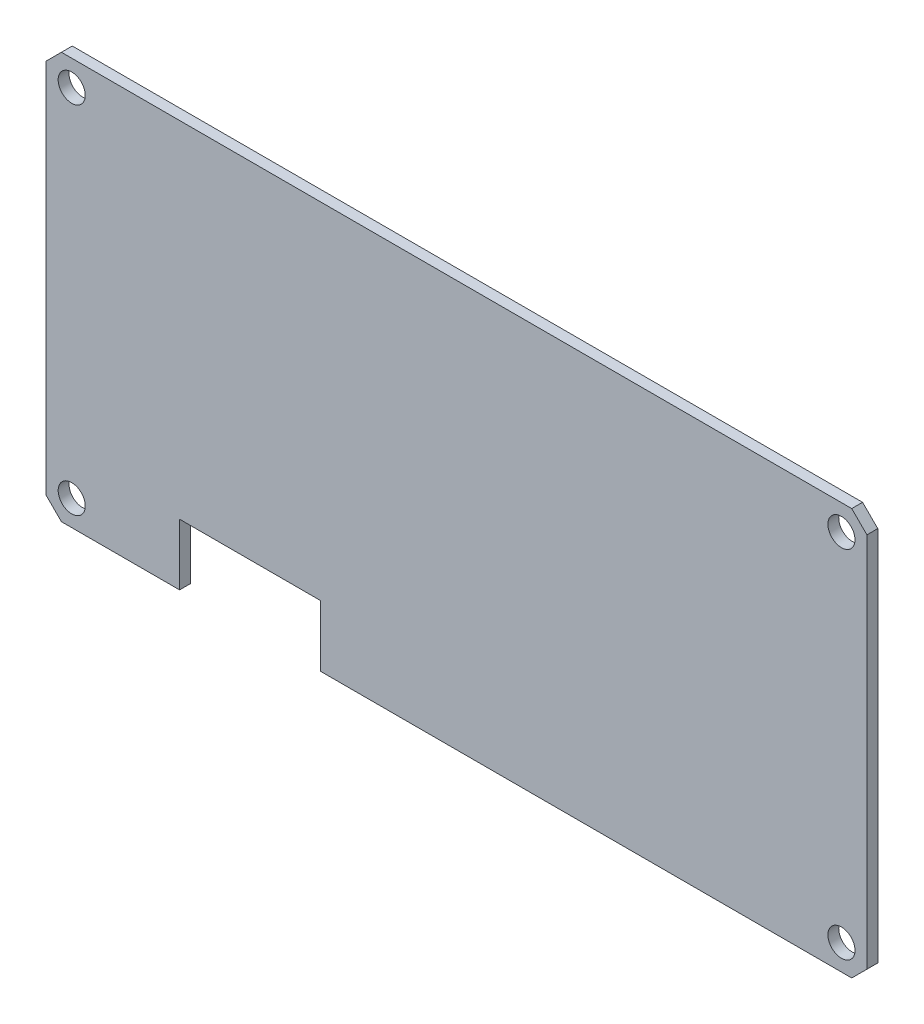
SolidWorks part; units mm, degrees
ref_plane "Front Plane" through (0, 0, 0) normal (0, 0, 1) x (1, 0, 0)
ref_plane "Top Plane" through (0, 0, 0) normal (0, 1, 0) x (1, 0, 0)
ref_plane "Right Plane" through (0, 0, 0) normal (1, 0, 0) x (0, 0, -1)
sketch "Sketch1" plane through (0, 0, 0) normal (0, 0, 1) x (1, 0, 0)
  line L1 (0, -18.75) -> (-33.8, -18.75)
  line L2 (0, -18.75) -> (0, 18.75)
  line L3 (0, 18.75) -> (-33.8, 18.75)
  line L4 (-33.8, -18.75) -> (-33.8, 18.75)
  line L5 (-31.8, -4.9) -> (-31.8, -14.1) construction
  dimension "D1" = 37.5
  dimension "D2" = 2
extrude "Boss-Extrude-NoAnt" add sketch "Sketch1" along normal blind 1
sketch "Sketch2" plane through (0, 0, 0) normal (0, 0, 1) x (1, 0, 0)
  line L1 (0, 18.75) -> (41.9, 18.75)
  line L2 (0, 18.75) -> (0, -18.75)
  line L3 (0, -18.75) -> (41.9, -18.75)
  line L4 (41.9, 18.75) -> (41.9, -18.75)
  line L5 (-33.8, -18.75) -> (0, -18.75) construction
  dimension "D1" = 41.9
extrude "Boss-Extrude-Ant" add sketch "Sketch2" along normal up to surface (1 mm away) up to face at (-16.9, 0, 1)
sketch "Sketch3" plane through (0, 0, 0) normal (0, 0, -1) x (-1, 0, 0)
  line L0 (31.45, -16.4) -> (-39.55, -16.4) construction
  line L1 (-39.55, -16.4) -> (-39.55, 16.4) construction
  line L2 (-39.55, 16.4) -> (31.45, 16.4) construction
  line L3 (31.45, 16.4) -> (31.45, -16.4) construction
  line L4 (-41.9, 18.75) -> (33.8, 18.75) construction
  line L5 (31.45, 16.4) -> (31.45, 18.75) construction
  line L6 (31.45, 16.4) -> (33.8, 16.4) construction
  line L7 (33.8, 18.75) -> (33.8, -18.75) construction
  line L8 (-39.55, 16.4) -> (-41.9, 16.4) construction
  line L9 (-41.9, -18.75) -> (-41.9, 18.75) construction
  line L10 (31.45, -16.4) -> (31.45, -18.75) construction
  line L11 (33.8, -18.75) -> (-41.9, -18.75) construction
  circle A0 centre (31.45, -16.4) radius 1.25
  circle A1 centre (-39.55, -16.4) radius 1.25
  circle A2 centre (-39.55, 16.4) radius 1.25
  circle A3 centre (31.45, 16.4) radius 1.25
  dimension "D1" = 2.5
  dimension "D2" = 2.35
extrude "Holes" cut sketch "Sketch3" against normal through all
sketch "Sketch4" plane through (0, 0, 0) normal (0, 0, -1) x (-1, 0, 0)
  line L0 (-41.9, 18.75) -> (-40.5, 18.75)
  line L1 (-41.9, 18.75) -> (33.8, 18.75) construction
  line L2 (-40.5, 18.75) -> (-41.9, 17.35)
  line L3 (-41.9, -18.75) -> (-41.9, 18.75) construction
  line L4 (-41.9, 17.35) -> (-41.9, 18.75)
  line L5 (-41.4626, 16.2552) -> (-39.3888, 18.3289) construction
  line L6 (-4.05, 18.75) -> (-4.05, -18.75) construction
  line L7 (33.8, -18.75) -> (-41.9, -18.75) construction
  line L8 (-41.9, 0) -> (33.8, 0) construction
  line L9 (33.8, 18.75) -> (33.8, -18.75) construction
  line L10 (-41.9, -17.35) -> (-41.9, -18.75)
  line L11 (-40.5, -18.75) -> (-41.9, -17.35)
  line L12 (-41.9, -18.75) -> (-40.5, -18.75)
  line L13 (33.8, -18.75) -> (32.4, -18.75)
  line L14 (32.4, -18.75) -> (33.8, -17.35)
  line L15 (33.8, -17.35) -> (33.8, -18.75)
  line L16 (33.8, 17.35) -> (33.8, 18.75)
  line L17 (32.4, 18.75) -> (33.8, 17.35)
  line L18 (33.8, 18.75) -> (32.4, 18.75)
  circle A0 centre (-39.55, 16.4) radius 1.25 construction
  dimension "D1" = 1.4
  dimension "D2" = 1.0835
extrude "Corners" cut sketch "Sketch4" against normal through all
sketch "Sketch5" plane through (0, 0, 1) normal (0, 0, 1) x (1, 0, 0)
  line L0 (-32.4, -18.75) -> (40.5, -18.75) construction
  line L1 (-21.5, -18.75) -> (-8.5, -18.75)
  line L2 (-21.5, -18.75) -> (-21.5, -13.1)
  line L3 (-21.5, -13.1) -> (-8.5, -13.1)
  line L4 (-8.5, -18.75) -> (-8.5, -13.1)
  line L5 (-33.8, 17.35) -> (-33.8, -17.35) construction
  dimension "D1" = 25.3
  dimension "D2" = 5.65
  dimension "D3" = 13
extrude "Cut-Extrude1" cut sketch "Sketch5" against normal through all
